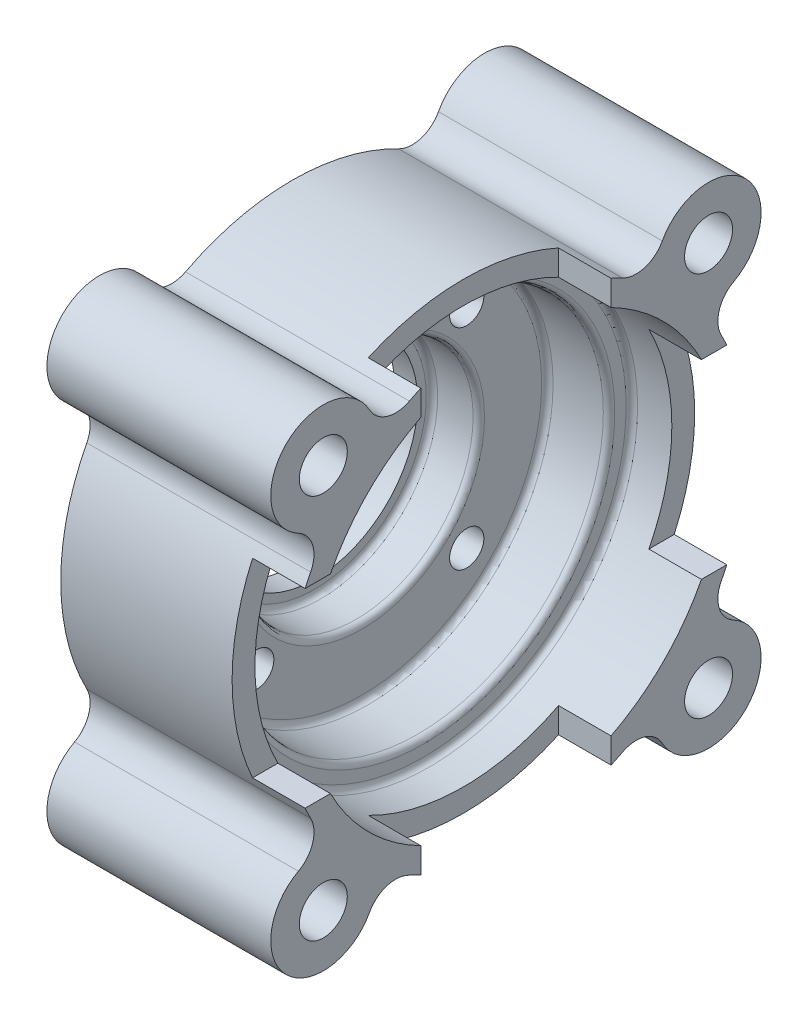
SolidWorks part; units mm, degrees
material "ABS"
ref_plane "Спереди" through (0, 0, 0) normal (0, 0, 1) x (1, 0, 0)
ref_plane "Сверху" through (0, 0, 0) normal (0, 1, 0) x (1, 0, 0)
ref_plane "Справа" through (0, 0, 0) normal (1, 0, 0) x (0, 0, -1)
sketch "Эскиз1" plane through (0, 0, 0) normal (1, 0, 0) x (0, 0, -1)
  circle A0 centre (0, 0) radius 20.25
  dimension "D1" = 40.5
extrude "Бобышка-Вытянуть1" add sketch "Эскиз1" along normal blind 2
sketch "Эскиз2" plane through (0, 0, 0) normal (-1, 0, 0) x (0, 0, 1)
  circle A0 centre (0, 0) radius 3.5
  dimension "D1" = 7
extrude "Вырез-Вытянуть1" cut sketch "Эскиз2" against normal through all
sketch "Эскиз3" plane through (2, 0, 0) normal (1, 0, 0) x (0, 0, -1)
  circle A0 centre (0, 0) radius 10.25
  circle A1 centre (0, 0) radius 20.25
  circle A2 centre (0, 0) radius 20.25 construction
  dimension "D1" = 20.5
extrude "Бобышка-Вытянуть2" add sketch "Эскиз3" along normal blind 4.1
sketch "Эскиз5" plane through (6.1, 0, 0) normal (1, 0, 0) x (0, 0, -1)
  circle A0 centre (0, 0) radius 16.25
  circle A1 centre (0, 0) radius 20.25
  circle A2 centre (0, 0) radius 20.25 construction
  dimension "D2" = 32.5
extrude "Бобышка-Вытянуть3" add sketch "Эскиз5" along normal blind 5.4
sketch "Эскиз6" plane through (11.5, 0, 0) normal (1, 0, 0) x (0, 0, -1)
  circle A0 centre (0, 0) radius 18.25
  circle A1 centre (0, 0) radius 20.25
  circle A2 centre (0, 0) radius 20.25 construction
  dimension "D2" = 36.5
extrude "Бобышка-Вытянуть4" add sketch "Эскиз6" along normal blind 100 and the other way blind 10
sketch "Эскиз7" plane through (0, 0, 0) normal (-1, 0, 0) x (0, 0, 1)
  line L0 (0, 0) -> (-14.3189, -14.3189) construction
  line L1 (-14.3189, -14.3189) -> (14.3189, 14.3189) construction
  line L2 (0, 0) -> (-14.3189, 14.3189) construction
  line L3 (-14.3189, 14.3189) -> (14.3189, -14.3189) construction
  circle A0 centre (0, 0) radius 20.25 construction
  circle A1 centre (-9.1924, 9.1924) radius 1.5
  dimension "D1" = 13
  dimension "D2" = 3
extrude "Вырез-Вытянуть2" cut sketch "Эскиз7" against normal through all
pattern_circular "Круговой массив1" count 4 over 360 about axis through (0, 0, 0) along (-1, 0, 0) of "Вырез-Вытянуть2"
fillet "Скругление1" radius 0.5 5 edges at (6.1, 0, -10.25) (11.5, 0, -16.25) (6.1, 0, -16.25) (11.5, 0, -18.25) (2, 0, -10.25)
sketch "Эскиз9" plane through (0, 0, 0) normal (-1, 0, 0) x (0, 0, 1)
  line L0 (-21.4838, 21.4838) -> (21.4838, -21.4838) construction
  line L1 (21.4838, 21.4838) -> (-21.4838, -21.4838) construction
  line L2 (0, 0) -> (0, 20.25) construction
  circle A0 centre (0, 0) radius 20.25 construction
  circle A1 centre (-16.8645, 16.8645) radius 2.1
  circle A2 centre (-16.8645, 16.8645) radius 4.6
  point P4 (0, 0)
  point P6 (0, 0)
  point P27 (0, 0)
  dimension "D3" = 4.2
  dimension "D4" = 9.2
  dimension "D1" = 45
  dimension "D2" = 45
  dimension "D5" = 23.85
extrude "Бобышка-Вытянуть6" add sketch "Эскиз9" against normal up to surface (111.5 mm away) up to face at (111.5, 0, -20.25)
sketch "Эскиз10" plane through (0, 0, 0) normal (-1, 0, 0) x (0, 0, 1)
  line L0 (-16.8645, 16.8645) -> (-9.1924, 9.1924) construction
  arc A0 (-12.8153, 19.0472) -> (-9.3288, 17.9732) centre (-10.5266, 20.2808) ccw
  arc A1 (-9.3288, 17.9732) -> (-12.3355, 16.0592) centre (0, 0) ccw
  arc A2 (-16.0592, 12.3355) -> (-12.3355, 16.0592) centre (0, 0) ccw construction
  arc A3 (-19.0472, 12.8153) -> (-12.8153, 19.0472) centre (-16.8645, 16.8645) ccw
  circle A4 centre (-16.8645, 16.8645) radius 4.6 construction
  arc A5 (-19.0472, 12.8153) -> (-17.9732, 9.3288) centre (-20.2808, 10.5266) cw
  arc A6 (-16.0592, 12.3355) -> (-17.9732, 9.3288) centre (0, 0) ccw
  arc M15 (-16.0592, 12.3355) -> (-12.3355, 16.0592) centre (0, 0) ccw
  arc M16 (-12.3355, 16.0592) -> (-16.0592, 12.3355) centre (-16.8645, 16.8645) ccw
  dimension "D1" = 2.6
extrude "Бобышка-Вытянуть7" add sketch "Эскиз10" against normal up to surface (111.5 mm away) contours A0 M16 M15 | A5 M16 M15 region at (0, 17.3535, -11.592) region at (0, 11.592, -17.3535) up to face at (111.5, 2.8991, -2.8991)
pattern_circular "Круговой массив3" count 4 over 360 about axis through (2, 0, 0) along (-1, 0, 0) of "Бобышка-Вытянуть7", "Бобышка-Вытянуть6"
sketch "Эскиз11" plane through (111.5, 0, 0) normal (1, 0, 0) x (0, 0, -1)
  line L1 (-32.25, 11.5) -> (-20.25, 11.5)
  line L2 (-32.25, 11.5) -> (-32.25, -23.5)
  line L3 (-32.25, -23.5) -> (-20.25, -23.5)
  line L4 (-20.25, 11.5) -> (-20.25, -23.5)
  arc A0 (-17.9732, 9.3288) -> (-17.9732, -9.3288) centre (0, 0) ccw construction
  point P7 (-20.25, -6)
  dimension "D1" = 12
  dimension "D2" = 35
  dimension "D3" = 6
extrude "Вырез-Вытянуть3" cut sketch "Эскиз11" against normal blind 26 from offset 42.75 offset against normal yes
ref_plane "Плоскость1" through (55.75, 0, 0) normal (-1, 0, 0) x (0, 0, 1)
sketch "Эскиз17" plane through (2, 0, 0) normal (1, 0, 0) x (0, 0, -1)
  circle A0 centre (0, 0) radius 9
  dimension "D1" = 18
extrude "Вырез-Вытянуть5" cut sketch "Эскиз17" against normal through all
ref_plane "Плоскость3" through (68.75, 0, 0) normal (1, 0, 0) x (0, 0, -1)
ref_plane "Плоскость4" through (42.75, 0, 0) normal (-1, 0, 0) x (0, 0, 1)
sketch "Эскиз19" plane through (111.5, 0, 0) normal (1, 0, 0) x (0, 0, -1)
  line L1 (21.4129, 16.1776) -> (21.4129, -16.1776)
  arc A0 (19.0472, 12.8153) -> (17.9732, 9.3288) centre (20.2808, 10.5266) ccw
  arc A1 (17.9732, -9.3288) -> (19.0472, -12.8153) centre (20.2808, -10.5266) ccw
  arc A2 (17.9732, -9.3288) -> (17.9732, 9.3288) centre (0, 0) ccw
  arc A3 (17.9732, -9.3288) -> (17.9732, 9.3288) centre (0, 0) ccw construction
  arc A4 (19.0472, 12.8153) -> (17.9732, 9.3288) centre (20.2808, 10.5266) ccw construction
  arc A5 (17.9732, -9.3288) -> (19.0472, -12.8153) centre (20.2808, -10.5266) ccw construction
  arc A6 (19.0472, 12.8153) -> (21.4129, 16.1776) centre (16.8645, 16.8645) ccw
  arc A7 (19.0472, 12.8153) -> (12.8153, 19.0472) centre (16.8645, 16.8645) ccw construction
  arc A8 (21.4129, -16.1776) -> (19.0472, -12.8153) centre (16.8645, -16.8645) ccw
  arc A9 (12.8153, -19.0472) -> (19.0472, -12.8153) centre (16.8645, -16.8645) ccw construction
  arc M8 (12.8153, -19.0472) -> (19.0472, -12.8153) centre (16.8645, -16.8645) ccw
  arc M9 (19.0472, -12.8153) -> (17.9732, -9.3288) centre (20.2808, -10.5266) cw
  arc M10 (17.9732, -9.3288) -> (17.9732, 9.3288) centre (0, 0) ccw
  arc M11 (17.9732, 9.3288) -> (19.0472, 12.8153) centre (20.2808, 10.5266) cw
  arc M12 (19.0472, 12.8153) -> (12.8153, 19.0472) centre (16.8645, 16.8645) ccw
extrude "Бобышка-Вытянуть14" add sketch "Эскиз19" against normal up to surface (68.75 mm away) from surface contours L1 M12 M11 M10 | L1 M10 M9 M8 region at (111.5, 0, -21.0872) up to plane "Плоскость4" starting at plane "Плоскость3"
ref_plane "Плоскость8" through (0, 0, 21.4645) normal (0, 0, 1) x (1, 0, 0)
sketch "Эскиз21" plane through (0, 0, 21.4645) normal (0, 0, 1) x (1, 0, 0)
  line L1 (42.75, 8.3288) -> (15, 8.3288)
  line L2 (42.75, 8.3288) -> (42.75, -8.3288)
  line L3 (42.75, -8.3288) -> (15, -8.3288)
  line L4 (15, 8.3288) -> (15, -8.3288)
  line L5 (55.75, 21.4645) -> (55.75, -21.4645) construction
  line L6 (15, 8.3288) -> (15, 9.3288) construction
  line L7 (111.5, 9.3288) -> (0, 9.3288) construction
  line L8 (15, -8.3288) -> (15, -9.3288) construction
  line L9 (111.5, -9.3288) -> (0, -9.3288) construction
  line L10 (111.5, 21.4645) -> (0, 21.4645) construction
  line L14 (0, 9.3288) -> (0, -9.3288) construction
  line L15 (0, -21.4645) -> (111.5, -21.4645) construction
  line L17 (96.5, -8.3288) -> (96.5, -9.3288) construction
  line L18 (96.5, 8.3288) -> (96.5, 9.3288) construction
  line L19 (96.5, 8.3288) -> (96.5, -8.3288)
  line L20 (68.75, -8.3288) -> (96.5, -8.3288)
  line L21 (68.75, 8.3288) -> (68.75, -8.3288)
  line L22 (68.75, 8.3288) -> (96.5, 8.3288)
  dimension "D1" = 1
  dimension "D4" = 15
  dimension "D5" = 42.75
extrude "Вырез-Вытянуть6" cut sketch "Эскиз21" against normal through all
ref_plane "Плоскость5" through (0, 21.4645, 0) normal (0, 1, 0) x (1, 0, 0)
sketch "Эскиз22" plane through (0, 21.4645, 0) normal (0, 1, 0) x (1, 0, 0)
  line L0 (0, 9.3288) -> (0, -9.3288) construction
  line L1 (15, 8.3288) -> (96.5, 8.3288)
  line L2 (15, 8.3288) -> (15, -8.3288)
  line L3 (15, -8.3288) -> (96.5, -8.3288)
  line L4 (96.5, 8.3288) -> (96.5, -8.3288)
  line L5 (111.5, -9.3288) -> (111.5, 9.3288) construction
  line L6 (111.5, 9.3288) -> (0, 9.3288) construction
  line L7 (111.5, -9.3288) -> (0, -9.3288) construction
  dimension "D1" = 15
  dimension "D2" = 15
  dimension "D3" = 1
  dimension "D4" = 1
extrude "Вырез-Вытянуть7" cut sketch "Эскиз22" against normal through all
sketch "Эскиз23" plane through (0, 0, -21.4129) normal (0, 0, -1) x (-1, 0, 0)
  line L0 (-78.75, -21.4645) -> (-55.75, -21.4645) construction
  line L1 (-91.75, -19.3785) -> (-78.75, -19.3785)
  line L2 (-91.75, -19.3785) -> (-91.75, -33.3785)
  line L3 (-91.75, -33.3785) -> (-78.75, -33.3785)
  line L4 (-78.75, -19.3785) -> (-78.75, -33.3785)
  line L5 (-32.75, -19.3785) -> (-19.75, -19.3785)
  line L6 (-32.75, -19.3785) -> (-32.75, -33.3785)
  line L7 (-32.75, -33.3785) -> (-19.75, -33.3785)
  line L8 (-19.75, -19.3785) -> (-19.75, -33.3785)
  line L9 (-55.75, -21.4645) -> (-32.75, -21.4645) construction
  line L10 (-111.5, -12.8153) -> (-111.5, -21.4645) construction
  line L11 (-55.75, 21.4645) -> (-55.75, -21.4645) construction
  line L12 (0, 21.4645) -> (-111.5, 21.4645) construction
  line L13 (-111.5, -21.4645) -> (0, -21.4645) construction
  dimension "D3" = 14
  dimension "D4" = 13
  dimension "D5" = 19.75
extrude "Бобышка-Вытянуть16" add sketch "Эскиз23" against normal blind 2.26 from offset 3 offset against normal yes
sketch "Эскиз24" plane through (0, 0, -18.4129) normal (0, 0, -1) x (-1, 0, 0)
  line L0 (-78.75, -21.1961) -> (-91.75, -21.1961) construction
  line L2 (-32.75, -33.3785) -> (-19.75, -33.3785) construction
  line L4 (-91.75, -33.3785) -> (-78.75, -33.3785) construction
  circle A0 centre (-85.25, -27.6961) radius 1.35
  circle A1 centre (-26.25, -27.6961) radius 1.35
  point P14 (-85.25, -33.3785)
  point P15 (-26.25, -33.3785)
  dimension "D1" = 2.7
  dimension "D2" = 2.7
  dimension "D4" = 6.5
extrude "Вырез-Вытянуть8" cut sketch "Эскиз24" against normal through all
sketch "Эскиз28" plane through (0, 0, -18.4129) normal (0, 0, -1) x (-1, 0, 0)
  line L0 (-78.75, -33.3785) -> (-78.75, -21.1961) construction
  line L1 (-91.75, -33.3785) -> (-78.75, -33.3785)
  line L2 (-91.75, -33.3785) -> (-91.75, -18.3785)
  line L3 (-91.75, -18.3785) -> (-78.75, -18.3785)
  line L4 (-78.75, -33.3785) -> (-78.75, -18.3785)
  line L5 (-19.75, -33.3785) -> (-19.75, -21.1961) construction
  line L6 (-32.75, -33.3785) -> (-19.75, -33.3785)
  line L7 (-32.75, -33.3785) -> (-32.75, -18.3785)
  line L8 (-32.75, -18.3785) -> (-19.75, -18.3785)
  line L9 (-19.75, -33.3785) -> (-19.75, -18.3785)
  circle A0 centre (-85.25, -27.6961) radius 3.1
  circle A1 centre (-26.25, -27.6961) radius 3.1
  dimension "D1" = 6.2
  dimension "D2" = 15
  dimension "D3" = 15
extrude "Бобышка-Вытянуть17" add sketch "Эскиз28" along normal blind 2.5
mirror "Зеркальное отражение1" about plane through (0, 0, 0) normal (0, 0, 1) of "Вырез-Вытянуть8", "Бобышка-Вытянуть16", "Бобышка-Вытянуть17"
fillet "Скругление4" radius 1 8 edges at (19.75, -33.3785, -18.5329) (19.75, -33.3785, 18.5329) (32.75, -33.3785, 18.5329) (32.75, -33.3785, -18.5329) (78.75, -33.3785, -18.5329) (78.75, -33.3785, 18.5329) (91.75, -33.3785, 18.5329) (91.75, -33.3785, -18.5329)
ref_plane "Плоскость7" through (0, -21.4645, 0) normal (0, -1, 0) x (-1, 0, 0)
sketch "Эскиз34" plane through (0, -21.4645, 0) normal (0, -1, 0) x (-1, 0, 0)
  line L0 (-96.5, -8.3288) -> (-96.5, 8.3288) construction
  line L1 (-111.5, 8.3288) -> (-96.5, 8.3288)
  line L2 (-111.5, 8.3288) -> (-111.5, -8.3288)
  line L3 (-111.5, -8.3288) -> (-96.5, -8.3288)
  line L4 (-96.5, 8.3288) -> (-96.5, -8.3288)
  line L5 (-111.5, 9.3288) -> (-111.5, -9.3288) construction
  line L6 (-96.5, 8.3288) -> (-15, 8.3288) construction
  line L7 (-15, -8.3288) -> (-96.5, -8.3288) construction
extrude "Вырез-Вытянуть15" cut sketch "Эскиз34" against normal up to surface (5.2259 mm away) up to face at (55.75, -17.2443, 0)
sketch "Эскиз35" plane through (0, 0, 21.4645) normal (0, 0, 1) x (1, 0, 0)
  line L0 (111.5, 12.8153) -> (0, 12.8153) construction
  line L1 (42.75, 12.8153) -> (32.75, 12.8153)
  line L2 (42.75, 12.8153) -> (42.75, 2.8153)
  line L3 (42.75, 2.8153) -> (32.75, 2.8153)
  line L4 (32.75, 12.8153) -> (32.75, 2.8153)
  line L5 (68.75, -8.3288) -> (68.75, 8.3288) construction
  line L6 (42.75, 8.3288) -> (42.75, -8.3288) construction
  line L11 (68.75, 12.8153) -> (78.75, 12.8153)
  line L12 (68.75, 12.8153) -> (68.75, 2.8153)
  line L13 (68.75, 2.8153) -> (78.75, 2.8153)
  line L14 (78.75, 12.8153) -> (78.75, 2.8153)
  dimension "D1" = 10
  dimension "D2" = 10
extrude "Бобышка-Вытянуть18" add sketch "Эскиз35" against normal up to surface and the other way blind 10 up to face at (63.25, -8.1193, 0)
sketch "Эскиз36" plane through (0, 0, 21.4645) normal (0, 0, 1) x (1, 0, 0)
  line L0 (42.75, 2.8153) -> (42.75, -8.3288) construction
  line L1 (32.75, -19.0486) -> (42.75, -19.0486)
  line L2 (32.75, -19.0486) -> (32.75, -29.0486)
  line L3 (32.75, -29.0486) -> (42.75, -29.0486)
  line L4 (42.75, -19.0486) -> (42.75, -29.0486)
  line L5 (68.75, -19.0486) -> (78.75, -19.0486)
  line L6 (68.75, -19.0486) -> (68.75, -29.0486)
  line L7 (68.75, -29.0486) -> (78.75, -29.0486)
  line L8 (78.75, -19.0486) -> (78.75, -29.0486)
  line L9 (68.75, -8.3288) -> (68.75, 2.8153) construction
  line L10 (19.75, -19.0486) -> (32.75, -19.0486) construction
  dimension "D1" = 10
  dimension "D2" = 10
extrude "Бобышка-Вытянуть19" add sketch "Эскиз36" against normal up to surface and the other way up to surface up to face at (26.25, -29.0461, 16.1529) other way up to face at (37.75, 7.8153, 31.4645)
sketch "Эскиз37" plane through (0, 0, 31.4645) normal (0, 0, 1) x (1, 0, 0)
  line L0 (42.75, 12.8153) -> (32.75, 2.8153) construction
  line L1 (78.75, 12.8153) -> (68.75, 2.8153) construction
  line L2 (42.75, -19.0486) -> (32.75, -29.0486) construction
  line L3 (78.75, -19.0486) -> (68.75, -29.0486) construction
  circle A0 centre (37.75, 7.8153) radius 1.5
  circle A1 centre (73.75, 7.8153) radius 1.5
  circle A2 centre (37.75, -24.0486) radius 1.5
  circle A3 centre (73.75, -24.0486) radius 1.5
  dimension "D1" = 3
extrude "Вырез-Вытянуть16" cut sketch "Эскиз37" against normal blind 20
sketch "Эскиз39" plane through (0, 0, 16.1529) normal (0, 0, -1) x (-1, 0, 0)
  line L1 (-70.7, -24.0486) -> (-72.225, -21.4072)
  line L2 (-72.225, -21.4072) -> (-75.275, -21.4072)
  line L3 (-75.275, -21.4072) -> (-76.8, -24.0486)
  line L4 (-76.8, -24.0486) -> (-75.275, -26.69)
  line L5 (-75.275, -26.69) -> (-72.225, -26.69)
  line L6 (-72.225, -26.69) -> (-70.7, -24.0486)
  line L7 (-34.7, -24.0486) -> (-36.225, -21.4072)
  line L8 (-36.225, -21.4072) -> (-39.275, -21.4072)
  line L9 (-39.275, -21.4072) -> (-40.8, -24.0486)
  line L10 (-40.8, -24.0486) -> (-39.275, -26.69)
  line L11 (-39.275, -26.69) -> (-36.225, -26.69)
  line L12 (-36.225, -26.69) -> (-34.7, -24.0486)
  line L14 (-78.75, -29.0486) -> (-68.75, -29.0486) construction
  line L17 (-42.75, -29.0486) -> (-32.75, -29.0486) construction
  circle A0 centre (-73.75, -24.0486) radius 3.05 construction
  circle A1 centre (-37.75, -24.0486) radius 3.05 construction
  dimension "D1" = 6.1
extrude "Вырез-Вытянуть17" cut sketch "Эскиз39" against normal blind 5
ref_plane "Плоскость9" through (0, 0, 15.4645) normal (0, 0, 1) x (1, 0, 0)
sketch "Эскиз40" plane through (0, 0, 15.4645) normal (0, 0, 1) x (1, 0, 0)
  line L1 (70.7, 7.8153) -> (72.225, 5.1739)
  line L2 (72.225, 5.1739) -> (75.275, 5.1739)
  line L3 (75.275, 5.1739) -> (76.8, 7.8153)
  line L4 (76.8, 7.8153) -> (75.275, 10.4567)
  line L5 (75.275, 10.4567) -> (72.225, 10.4567)
  line L6 (72.225, 10.4567) -> (70.7, 7.8153)
  line L7 (34.7, 7.8153) -> (36.225, 5.1739)
  line L8 (36.225, 5.1739) -> (39.275, 5.1739)
  line L9 (39.275, 5.1739) -> (40.8, 7.8153)
  line L10 (40.8, 7.8153) -> (39.275, 10.4567)
  line L11 (39.275, 10.4567) -> (36.225, 10.4567)
  line L12 (36.225, 10.4567) -> (34.7, 7.8153)
  circle A0 centre (73.75, 7.8153) radius 3.05 construction
  circle A1 centre (37.75, 7.8153) radius 3.05 construction
  dimension "D1" = 6.1
extrude "Вырез-Вытянуть18" cut sketch "Эскиз40" along normal blind 7
sketch "Эскиз41" plane through (0, 12.8153, 0) normal (0, 1, 0) x (1, 0, 0)
  line L1 (32.75, -31.4645) -> (78.75, -31.4645)
  line L2 (32.75, -31.4645) -> (32.75, -19.0472)
  line L3 (32.75, -19.0472) -> (78.75, -19.0472)
  line L4 (78.75, -31.4645) -> (78.75, -19.0472)
  line L6 (68.75, -19.0472) -> (78.75, -19.0472) construction
  line L7 (78.75, -31.4645) -> (78.75, -19.0472) construction
extrude "Вырез-Вытянуть19" cut sketch "Эскиз41" against normal blind 0.17
sketch "Эскиз42" plane through (42.75, 0, 0) normal (1, 0, 0) x (0, 0, -1)
  line L0 (-16.1529, -21.4091) -> (-16.1529, -29.0486)
  line L1 (-16.1529, -29.0486) -> (-31.4645, -29.0486)
  line L2 (-31.4645, -29.0486) -> (-31.4645, -19.0486)
  line L3 (-31.4645, -19.0486) -> (-20.9129, -19.0486)
  line L4 (-20.25, -13.7503) -> (-20.25, -19.9787)
  line L5 (-20.25, -19.9787) -> (-20.25, -13.7503) construction
  line L6 (-19.0472, 12.8153) -> (-19.0472, 12.6453)
  line L7 (-19.0472, 12.6453) -> (-31.4645, 12.6453)
  line L8 (-31.4645, 12.6453) -> (-31.4645, 2.8153)
  line L9 (-31.4645, 2.8153) -> (-20.0533, 2.8153)
  arc A0 (-20.25, -13.7503) -> (-20.9129, -19.0486) centre (-16.8645, -16.8645) ccw
  arc A1 (-20.25, -19.9787) -> (-16.1529, -21.4091) centre (-16.8645, -16.8645) ccw
  arc A2 (-17.9732, 9.3288) -> (-19.0472, 12.8153) centre (-20.2808, 10.5266) ccw
  arc A3 (-17.9732, 9.3288) -> (-19.0472, 12.8153) centre (-20.2808, 10.5266) ccw construction
  arc A4 (-17.9732, 9.3288) -> (-20.0533, 2.8153) centre (0, 0) ccw
  arc A5 (-17.9732, 9.3288) -> (-20.0533, 2.8153) centre (0, 0) ccw construction
  arc M8 (-20.25, -13.7503) -> (-20.9129, -19.0486) centre (-16.8645, -16.8645) ccw
  line M9 (-20.9129, -19.0486) -> (-31.4645, -19.0486)
  line M10 (-31.4645, -19.0486) -> (-31.4645, -29.0486)
  line M11 (-31.4645, -29.0486) -> (-16.1529, -29.0486)
  line M12 (-16.1529, -29.0486) -> (-16.1529, -21.4091)
  arc M13 (-16.1529, -21.4091) -> (-20.25, -19.9787) centre (-16.8645, -16.8645) cw
  line M14 (-20.25, -19.9787) -> (-20.25, -13.7503)
extrude "Вырез-Вытянуть20" cut sketch "Эскиз42" against normal blind 0.15 contours A4 A2 L6 L7 L8 L9 | M14 M8 M9 M10 M11 M12 M13 region at (42.75, -24.0291, 24.0346) region at (42.75, 7.8967, 25.0962)
mirror "Зеркальное отражение2" about plane through (55.75, 0, 0) normal (-1, 0, 0) of "Вырез-Вытянуть20"
sketch "Эскиз43" plane through (0, 0, 21.4645) normal (0, 0, 1) x (1, 0, 0)
  line L0 (111.5, -21.4645) -> (111.5, -12.8153) construction
  line L1 (91.75, -21.4645) -> (111.5, -21.4645) construction
  circle A0 centre (94.75, -13.4545) radius 3.5
  circle A1 centre (94.75, -13.4545) radius 1.35
  dimension "D1" = 7
  dimension "D2" = 2.7
  dimension "D3" = 16.75
  dimension "D4" = 8.01
extrude "Бобышка-Вытянуть20" add sketch "Эскиз43" against normal up to next
sketch "Эскиз44" plane through (0, 0, 21.4645) normal (0, 0, 1) x (1, 0, 0)
  circle A0 centre (94.75, -13.4545) radius 1.35
extrude "Вырез-Вытянуть21" cut sketch "Эскиз44" against normal up to surface (9.1341 mm away) up to face at (73.75, 7.5716, 16.5121)
sketch "Эскиз48" plane through (0, 0, 21.4645) normal (0, 0, 1) x (1, 0, 0)
  line L0 (15, 8.3288) -> (32.75, 8.3288) construction
  line L1 (46.75, 8.3288) -> (64.75, 8.3288)
  line L2 (46.75, 8.3288) -> (46.75, -8.3288)
  line L3 (46.75, -8.3288) -> (64.75, -8.3288)
  line L4 (64.75, 8.3288) -> (64.75, -8.3288)
  line L5 (42.75, -8.3288) -> (15, -8.3288) construction
  line L8 (42.75, -8.3288) -> (46.75, -8.3288) construction
  line L9 (64.75, -8.3288) -> (68.75, -8.3288) construction
  dimension "D1" = 4
extrude "Вырез-Вытянуть26" cut sketch "Эскиз48" against normal up to surface (5.2259 mm away) up to face at (93.4, -13.4484, 12.337)
ref_axis "Ось1" through (12, 0, 0) along (1, 0, 0)
ref_point "ТочкаЦентр" [suppressed]
sketch "Эскиз49" [suppressed] plane through (0, 0, -29.3129) normal (0, 0, -1) x (-1, 0, 0)
  circle A0 centre (-55.75, 2.4276) radius 1.35
  dimension "D1" = 2.7
extrude "Вырез-Вытянуть27" [suppressed] cut sketch "Эскиз49" against normal blind 20
sketch "Эскиз50" plane through (0, 0, -21.4129) normal (0, 0, -1) x (-1, 0, 0)
  line L0 (-42.75, 16.1776) -> (-68.75, 16.1776) construction
  circle A0 centre (-55.75, 2.4276) radius 2.5
  dimension "D2" = 5
  dimension "D1" = 13.75
extrude "Вырез-Вытянуть28" cut sketch "Эскиз50" against normal blind 20
sketch "Эскиз51" plane through (0, 0, -21.4129) normal (0, 0, -1) x (-1, 0, 0)
  circle A0 centre (-55.75, 2.4276) radius 10
  circle A1 centre (-55.75, 2.4276) radius 2.5
  circle A2 centre (-55.75, 2.4276) radius 2.5 construction
  dimension "D1" = 20
extrude "Бобышка-Вытянуть21" add sketch "Эскиз51" along normal blind 5
fillet "Скругление5" radius 3 1 edges at (55.75, -7.5724, -21.4129)
sketch "Эскиз53" plane through (19.75, 0, 0) normal (-1, 0, 0) x (0, 0, 1)
  line L1 (-37.1939, 51.8577) -> (37.1939, 51.8577)
  line L2 (-37.1939, 51.8577) -> (-37.1939, -51.8577)
  line L3 (-37.1939, -51.8577) -> (37.1939, -51.8577)
  line L4 (37.1939, 51.8577) -> (37.1939, -51.8577)
  line L5 (-37.1939, 51.8577) -> (37.1939, -51.8577) construction
  line L6 (-37.1939, -51.8577) -> (37.1939, 51.8577) construction
  point P0 (0, 0)
extrude "Вырез-Вытянуть31" cut sketch "Эскиз53" against normal through all
sketch "Эскиз54" plane through (19.75, 0, 0) normal (1, 0, 0) x (0, 0, -1)
  line L1 (-28.9431, 26.3164) -> (28.9431, 26.3164)
  line L2 (-28.9431, 26.3164) -> (-28.9431, -26.3164)
  line L3 (-28.9431, -26.3164) -> (28.9431, -26.3164)
  line L4 (28.9431, 26.3164) -> (28.9431, -26.3164)
  line L5 (-28.9431, 26.3164) -> (28.9431, -26.3164) construction
  line L6 (-28.9431, -26.3164) -> (28.9431, 26.3164) construction
  point P0 (0, 0)
extrude "Вырез-Вытянуть32" cut sketch "Эскиз54" against normal blind 0.15
